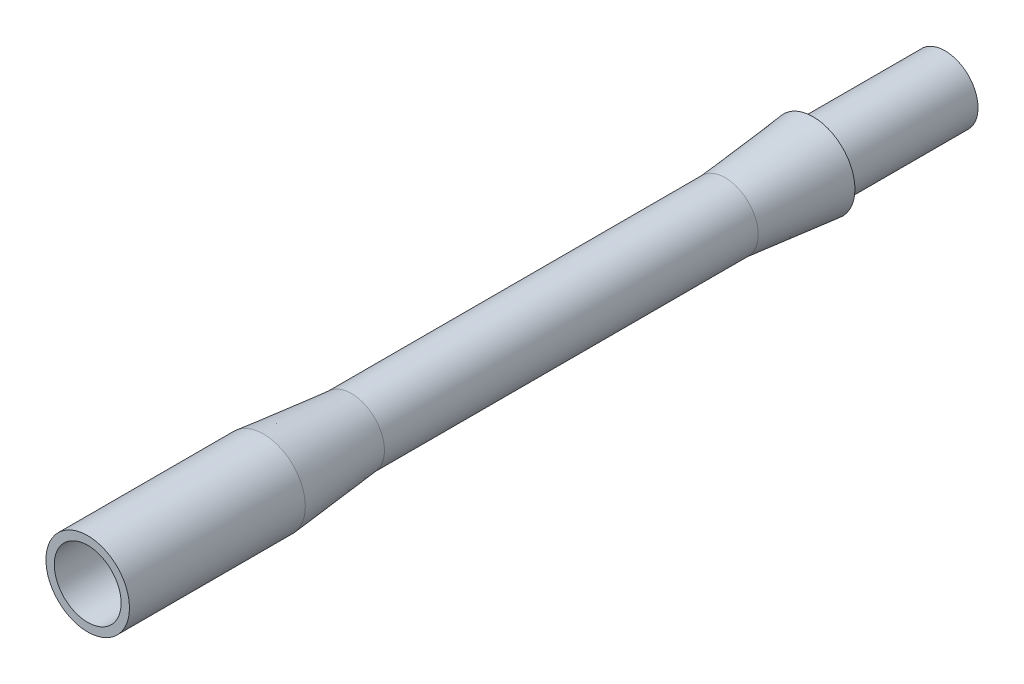
SolidWorks part; units mm, degrees
material "ABS"
ref_plane "Front Plane" through (0, 0, 0) normal (0, 0, 1) x (1, 0, 0)
ref_plane "Top Plane" through (0, 0, 0) normal (0, 1, 0) x (1, 0, 0)
ref_plane "Right Plane" through (0, 0, 0) normal (1, 0, 0) x (0, 0, -1)
sketch "Sketch1" plane through (0, 0, 0) normal (0, 0, 1) x (1, 0, 0)
  circle A0 centre (0, 0) radius 7.6
  circle A1 centre (0, 0) radius 9.5
  dimension "D1" = 15.2
  dimension "D2" = 19
extrude "Boss-Extrude1" add sketch "Sketch1" against normal blind 40
sketch "Sketch2" plane through (0, 0, -40) normal (0, 0, -1) x (-1, 0, 0)
  circle A0 centre (0, 0) radius 7.5
  circle A1 centre (0, 0) radius 6.5
  dimension "D1" = 15
  dimension "D2" = 13
extrude "Boss-Extrude2" add sketch "Sketch2" along normal blind 125 separate body
sketch "Sketch3" plane through (0, 0, 0) normal (1, 0, 0) x (0, 0, -1)
  line L0 (40, 7.5) -> (40, 9.5)
  line L1 (60, 7.5) -> (40, 7.5)
  line L2 (60, 7.5) -> (40, 9.5)
  line L3 (165, 7.5) -> (40, 7.5) construction
  line L4 (40, 0) -> (49.5295, 0)
  line L5 (40, -9.5) -> (40, 9.5) construction
revolve "Revolve1" add sketch "Sketch3" angle 360 about L4
sketch "Sketch4" plane through (0, 0, -165) normal (0, 0, -1) x (-1, 0, 0)
  circle A0 centre (0, 0) radius 6.5
  circle A1 centre (0, 0) radius 5.75
  dimension "D1" = 11.5
extrude "Boss-Extrude3" add sketch "Sketch4" against normal up to surface (125 mm away) up to face at (7.6, 0, -40)
sketch "Sketch5" plane through (0, 0, -165) normal (0, 0, -1) x (-1, 0, 0)
  circle A0 centre (0, 0) radius 5.75
  circle A1 centre (0, 0) radius 7.5
  dimension "D1" = 11.5
extrude "Boss-Extrude4" add sketch "Sketch5" along normal blind 30
sketch "Sketch6" plane through (0, 0, 0) normal (1, 0, 0) x (0, 0, -1)
  line L0 (195, 0) -> (185.163, 0)
  line L1 (195, 7.5) -> (60, 7.5) construction
  line L2 (165, 7.5) -> (165, 9.5)
  line L3 (165, 7.5) -> (145, 7.5)
  line L4 (145, 7.5) -> (165, 9.5)
  line L5 (195, -7.5) -> (195, 7.5) construction
  dimension "D2" = 2
  dimension "D3" = 20
revolve "Revolve2" add sketch "Sketch6" angle 360 about L0
sketch "Sketch7" plane through (0, 0, 0) normal (1, 0, 0) x (0, 0, -1)
  line L0 (40, 0) -> (37.2181, 0)
  line L1 (40, 9.5) -> (40, -9.5) construction
  line L2 (40, 5.75) -> (40, 7.6)
  line L4 (40, 5.75) -> (38.15, 7.6)
  line L5 (40, 7.6) -> (0, 7.6) construction
  line L6 (38.15, 7.6) -> (40, 7.6)
revolve "Revolve3" add sketch "Sketch7" angle 360 about L0 region at (0, 6.9833, -39.3833)
